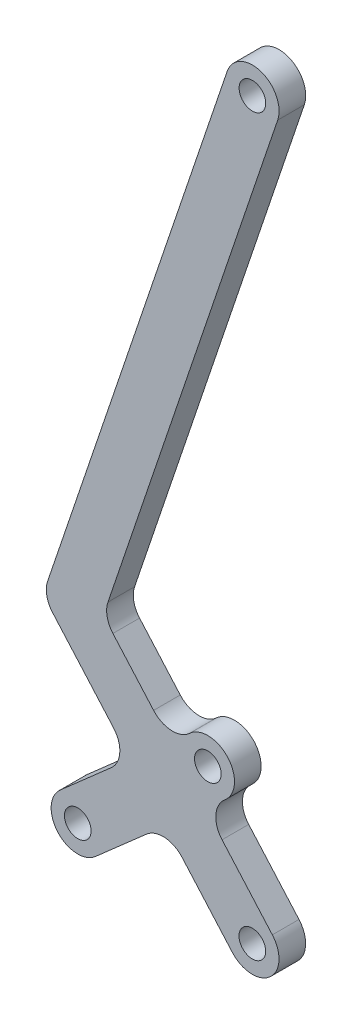
SolidWorks part; units mm, degrees
ref_plane "Front Plane" through (0, 0, 0) normal (0, 0, 1) x (1, 0, 0)
ref_plane "Top Plane" through (0, 0, 0) normal (0, 1, 0) x (1, 0, 0)
ref_plane "Right Plane" through (0, 0, 0) normal (1, 0, 0) x (0, 0, -1)
sketch "Sketch1" plane through (0, 0, 0) normal (0, 0, 1) x (1, 0, 0)
  line L1 (-47.8616, 100.1191) -> (-133.4426, -153.1446)
  line L2 (-26.3356, -245.5597) -> (-50.3076, -218.301)
  line L3 (-104.6847, -147.383) -> (-23.7983, 91.9878)
  line L4 (-131.0852, -164.9108) -> (-102.0042, -197.979)
  line L5 (-106.9026, -153.9466) -> (-130.9659, -145.8153) construction
  line L6 (-106.9026, -153.9466) -> (-125.9761, -170.7203) construction
  line L7 (-65.9949, -182.2917) -> (-65.4692, -181.8294)
  line L8 (-49.2211, -201.3653) -> (-48.6954, -200.903)
  line L9 (-58.2322, -209.2899) -> (-77.3058, -226.0637) construction
  line L10 (-82.9306, -181.2052) -> (-102.3273, -159.1491)
  line L11 (-103.0907, -214.9147) -> (-127.4582, -236.3442)
  line L12 (-86.3169, -233.9883) -> (-110.6845, -255.4178)
  line L13 (-69.3811, -235.0748) -> (-45.4092, -262.3334)
  line L14 (-75.006, -190.2163) -> (-94.0795, -206.9901) construction
  arc A0 (-23.7983, 91.9878) -> (-47.8616, 100.1191) centre (-35.83, 96.0534) ccw
  arc A1 (-45.4092, -262.3334) -> (-26.3356, -245.5597) centre (-35.8724, -253.9466) ccw
  arc A2 (-65.4692, -181.8294) -> (-48.6954, -200.903) centre (-57.0823, -191.3662) cw
  arc A3 (-127.4582, -236.3442) -> (-110.6845, -255.4178) centre (-119.0714, -245.881) ccw
  arc A4 (-103.0907, -214.9147) -> (-102.0042, -197.979) centre (-111.0153, -205.9036) ccw
  arc A5 (-69.3811, -235.0748) -> (-86.3169, -233.9883) centre (-78.3923, -242.9994) ccw
  arc A6 (-50.3076, -218.301) -> (-49.2211, -201.3653) centre (-41.2965, -210.3764) cw
  arc A7 (-65.9949, -182.2917) -> (-82.9306, -181.2052) centre (-73.9195, -173.2806) cw
  arc A8 (-133.4426, -153.1446) -> (-131.0852, -164.9108) centre (-122.0741, -156.9862) ccw
  arc A9 (-102.3273, -159.1491) -> (-104.6847, -147.383) centre (-93.3162, -151.2245) cw
  circle A10 centre (-57.0823, -191.3662) radius 6.35
  circle A11 centre (-119.0714, -245.881) radius 6.35
  circle A12 centre (-35.8724, -253.9466) radius 6.35
  circle A13 centre (-35.83, 96.0534) radius 6.35
  point P41 (-171.8588, -192.9041)
  dimension "D9" = 12.7
  dimension "D10" = 12
  dimension "D11" = 12.7
  dimension "D12" = 44.45
  dimension "D1" = 350
  dimension "D2" = 25.4
  dimension "D3" = 250
  dimension "D4" = 120
  dimension "D5" = 25.4
  dimension "D6" = 12.7
  dimension "D7" = 122
  dimension "D8" = 48.3
extrude "Boss-Extrude2" add sketch "Sketch1" along normal blind 12.7
